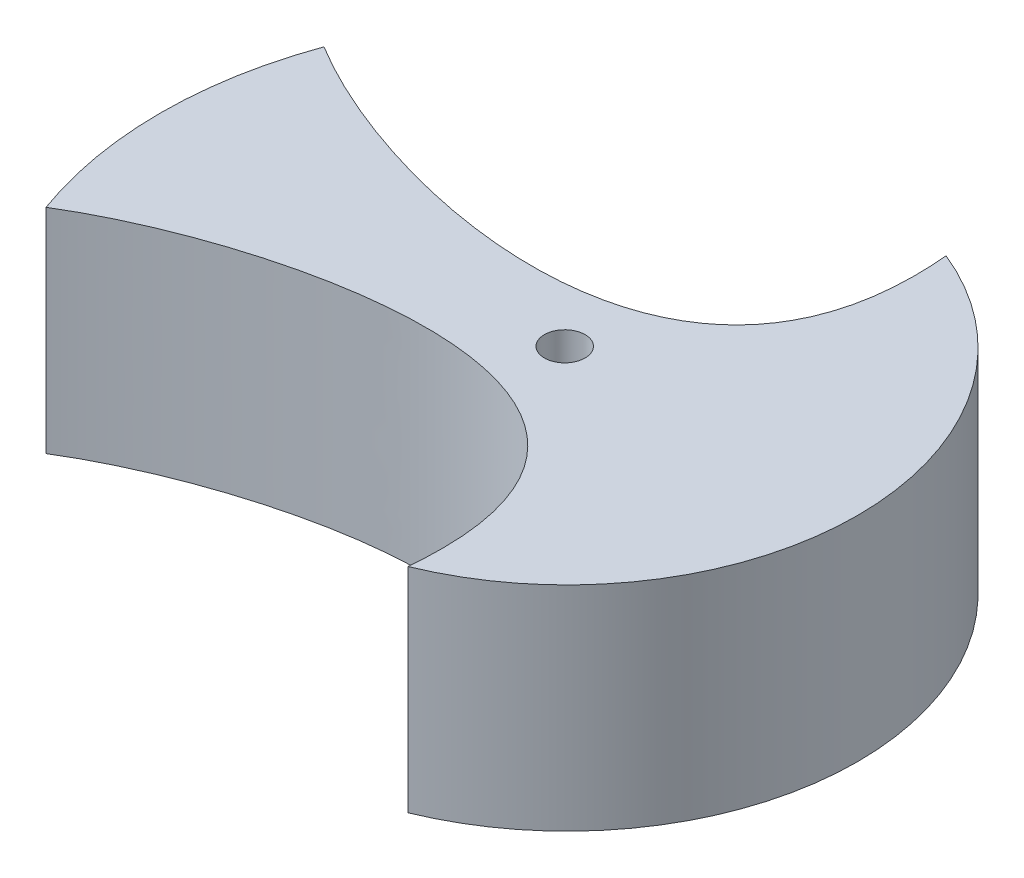
SolidWorks part; units mm, degrees
material "PLA"
ref_plane "Front Plane" through (0, 0, 0) normal (0, 0, 1) x (1, 0, 0)
ref_plane "Top Plane" through (0, 0, 0) normal (0, 1, 0) x (1, 0, 0)
ref_plane "Right Plane" through (0, 0, 0) normal (1, 0, 0) x (0, 0, -1)
other "Center of Mass"
sketch "Sketch2" plane through (0, 0, 0) normal (0, 1, 0) x (1, 0, 0)
  line L0 (0, 0) -> (-63.5, 0)
  line L1 (0, 0) -> (63.5, 0)
  circle A0 centre (0, 0) radius 63.5 construction
  arc A2 (-59.6705, -21.7183) -> (-59.6705, 21.7183) centre (0, 0) cw
  arc A3 (17.1974, -42.0478) -> (17.1974, 42.0478) centre (0, 0) ccw
  spline S0 degree 3 poles (-59.6705, 21.7183) (-35.8281, 6.9894) (21.7167, -5.9231) (17.1974, 42.0478) knots 0 0 0 0 1 1 1 1
  spline S1 degree 3 poles (-59.6705, -21.7183) (-35.8281, -6.9894) (21.7167, 5.9231) (17.1974, -42.0478) knots 0 0 0 0 1 1 1 1
  dimension "D1" = 127
  dimension "D2" = 160
extrude "Boss-Extrude1" add sketch "Sketch2" along normal up to surface (33.325 mm away) contours A2 L0 | S0 A2 L0 region at (22.7144, 0, 1.1676) region at (-31.75, 0, -1.1676)
other "Center of Mass Reference Point1"
sketch "Sketch3" plane through (0, 0, 0) normal (0, -1, 0) x (1, 0, 0)
  circle A0 centre (-0.338, 0.0001) radius 3.175
  dimension "D1" = 6.35
extrude "Cut-Extrude1" cut sketch "Sketch3" against normal through all
